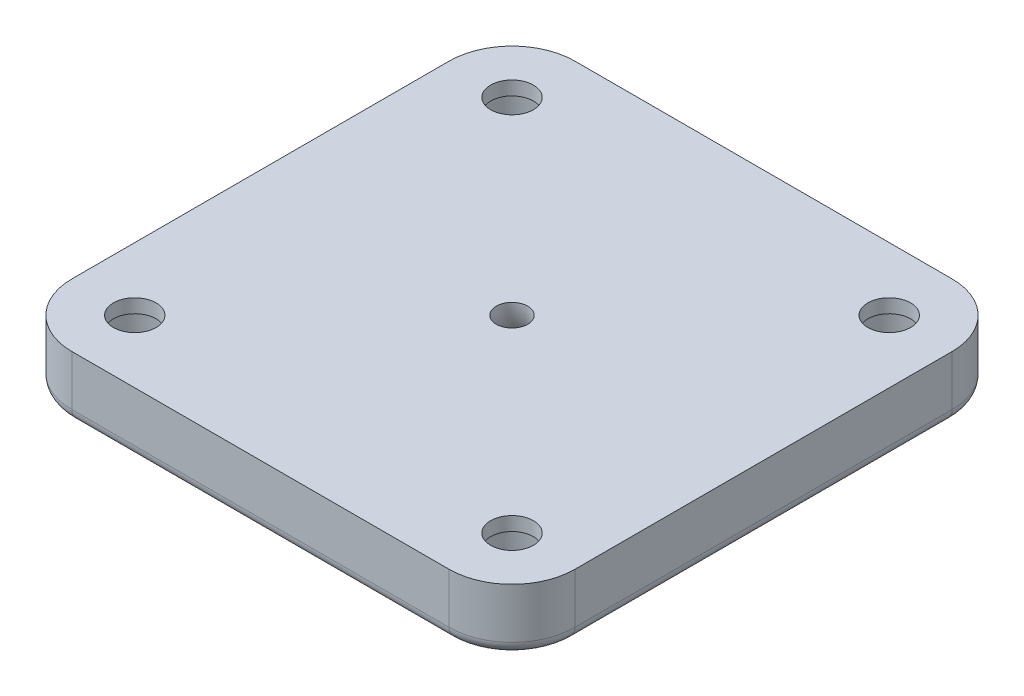
SolidWorks part; units mm, degrees
ref_plane "Front" through (0, 0, 0) normal (0, 0, 1) x (1, 0, 0)
ref_plane "Top" through (0, 0, 0) normal (0, 1, 0) x (1, 0, 0)
ref_plane "Right" through (0, 0, 0) normal (1, 0, 0) x (0, 0, -1)
sketch "Sketch1" plane through (0, -7, 0) normal (0, -1, 0) x (-1, 0, 0)
  line L4 (15, 20) -> (-15, 20)
  line L5 (-20, 15) -> (-20, -15)
  line L6 (-15, -20) -> (15, -20)
  line L7 (20, -15) -> (20, 15)
  line L8 (15, 20) -> (-15, 20)
  line L9 (-20, 15) -> (-20, -15)
  line L10 (-15, -20) -> (15, -20)
  line L11 (20, -15) -> (20, 15)
  circle A1 centre (-15, 15) radius 1.7
  circle A2 centre (-15, 15) radius 1.7
  circle A3 centre (15, 15) radius 1.7
  circle A4 centre (15, 15) radius 1.7
  circle A5 centre (-15, -15) radius 1.7
  circle A6 centre (-15, -15) radius 1.7
  circle A7 centre (15, -15) radius 1.7
  circle A8 centre (15, -15) radius 1.7
  circle A9 centre (0, 0) radius 1.25
  circle A10 centre (15, -15) radius 2.6
  circle A11 centre (-15, -15) radius 2.6
  arc A12 (20, 15) -> (15, 20) centre (15, 15) ccw
  arc A13 (-15, 20) -> (-20, 15) centre (-15, 15) ccw
  arc A14 (-20, -15) -> (-15, -20) centre (-15, -15) ccw
  arc A15 (15, -20) -> (20, -15) centre (15, -15) ccw
  arc A16 (20, 15) -> (15, 20) centre (15, 15) ccw
  arc A17 (-15, 20) -> (-20, 15) centre (-15, 15) ccw
  arc A18 (-20, -15) -> (-15, -20) centre (-15, -15) ccw
  arc A19 (15, -20) -> (20, -15) centre (15, -15) ccw
  circle A20 centre (-15, 15) radius 2.6
  circle A21 centre (15, 15) radius 2.6
  dimension "D6" = 5.2
  dimension "D7" = 5.2
  dimension "D8" = 5.2
  dimension "D9" = 5.2
  dimension "D10" = 2.5
  dimension "D1" = 0
  dimension "D2" = 0
  dimension "D3" = 0
  dimension "D4" = 0
  dimension "D5" = 0
extrude "Boss-Extrude1" add sketch "Sketch1" along normal blind 5 contours L10 A19 L11 A16 L8 A17 L9 A18
extrude "Cut-Extrude3" cut sketch "Sketch1<3>" along normal through all contours A8 | A6 | A4 | A2 | A9
sketch "Sketch1<3>" plane through (0, -7, 0) normal (0, -1, 0) x (-1, 0, 0) same geometry as "Sketch1"
extrude "Cut-Extrude4" cut sketch "Sketch1<4>" against normal blind 3.9 draft 1.5 from surface contours A10 | A11 | A21 | A20 starting at face at (15, -12, 13.3)
sketch "Sketch1<4>" plane through (0, -7, 0) normal (0, -1, 0) x (-1, 0, 0) same geometry as "Sketch1"
fillet "Fillet1" radius 5 1 edges at (0, -12, -1.25)
fillet "Fillet2" radius 1 8 edges at (18.5355, -12, -18.5355) (0, -12, -20) (-18.5355, -12, -18.5355) (-20, -12, 0) (-18.5355, -12, 18.5355) (0, -12, 20) (18.5355, -12, 18.5355) (20, -12, 0)
equation "\"D7@Sketch1\"=\"D6@Sketch1\""
equation "\"D8@Sketch1\"=\"D6@Sketch1\""
equation "\"D9@Sketch1\"=\"D6@Sketch1\""
